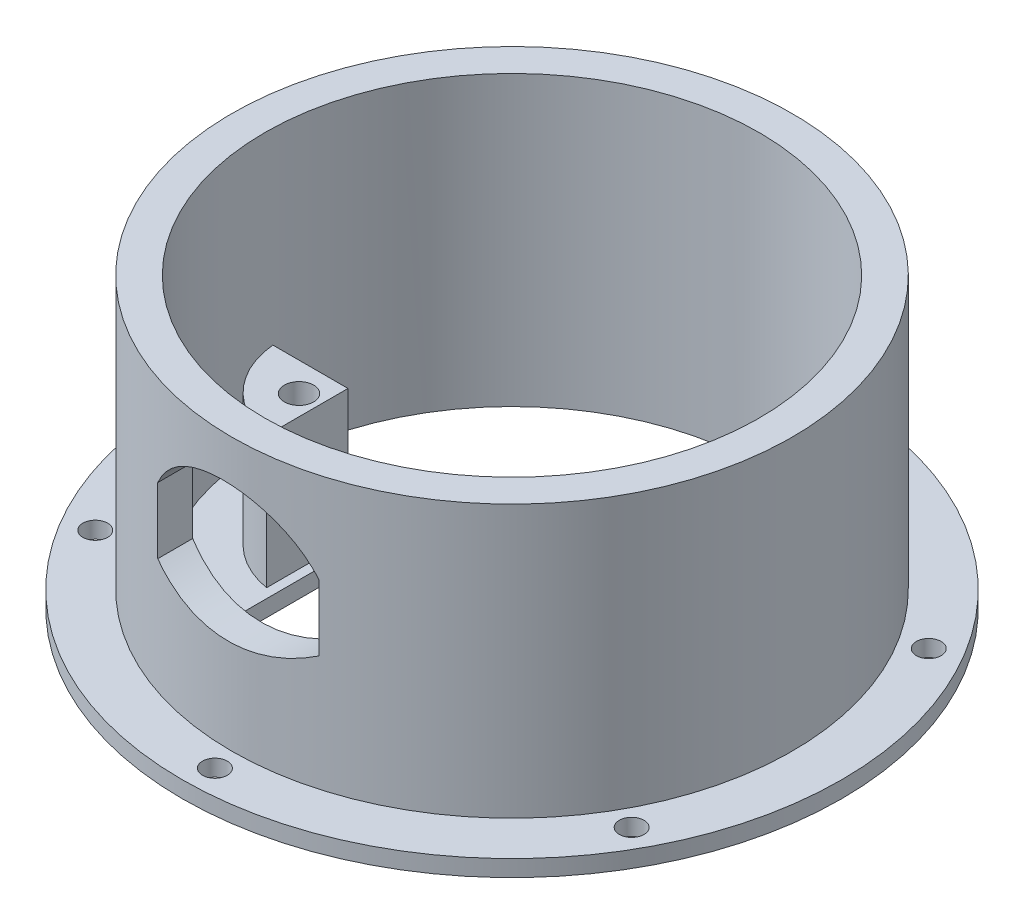
SolidWorks part; units mm, degrees
ref_plane "Front Plane" through (0, 0, 0) normal (0, 0, 1) x (1, 0, 0)
ref_plane "Top Plane" through (0, 0, 0) normal (0, 1, 0) x (1, 0, 0)
ref_plane "Right Plane" through (0, 0, 0) normal (1, 0, 0) x (0, 0, -1)
sketch "Sketch1" plane through (0, 0, 0) normal (0, 1, 0) x (1, 0, 0)
  circle A0 centre (0, 0) radius 40
  circle A1 centre (0, 0) radius 30
  dimension "D1" = 80
  dimension "D2" = 60
extrude "Boss-Extrude1" add sketch "Sketch1" along normal blind 2
sketch "Sketch2" plane through (0, 2, 0) normal (0, 1, 0) x (1, 0, 0)
  circle A0 centre (0, 0) radius 30 construction
  circle A1 centre (0, 0) radius 30
  circle A2 centre (0, 0) radius 34
  dimension "D1" = 4
extrude "Boss-Extrude2" add sketch "Sketch2" along normal blind 33
ref_plane "Plane1" through (0, 15, 0) normal (0, 1, 0) x (1, 0, 0)
sketch "Sketch9" plane through (0, 0, 0) normal (0, 1, 0) x (1, 0, 0)
  line L0 (-29.8657, -2.8351) -> (29.8657, -2.8351)
  line L1 (0, 30) -> (0, -48.3805) construction
  line L2 (-30, 0) -> (59.405, 0) construction
  circle A0 centre (0, 0) radius 30 construction
  arc A1 (29.8657, -2.8351) -> (0, -30) centre (0, 0) cw
  arc A2 (-29.8657, -2.8351) -> (0, -30) centre (0, 0) ccw
extrude "Boss-Extrude3" add sketch "Sketch9" along normal blind 2
sketch "Sketch11" plane through (0, 2, 0) normal (0, 1, 0) x (1, 0, 0)
  line L0 (-24.1735, -4.8351) -> (-15.0625, -4.8351)
  line L1 (-15.0625, -4.8351) -> (-15.0625, -14.7177)
  line L2 (0, 30) -> (0, 39.1404) construction
  line L3 (24.1735, -4.8351) -> (15.0625, -4.8351)
  line L4 (15.0625, -4.8351) -> (15.0625, -14.7177)
  line L5 (-29.8657, -2.8351) -> (29.8657, -2.8351) construction
  arc A0 (-24.1735, -4.8351) -> (-15.0625, -14.7177) centre (-13.1735, -3.8351) ccw
  arc A1 (24.1735, -4.8351) -> (15.0625, -14.7177) centre (13.1735, -3.8351) cw
  dimension "D1" = 2
ref_plane "Plane2" through (0, 0, 35) normal (0, 0, 1) x (1, 0, 0)
sketch "Sketch10" plane through (0, 0, 35) normal (0, 0, 1) x (1, 0, 0)
  line L1 (9.2889, 24.0041) -> (9.2889, 16.0041)
  line L2 (-10.7111, 24.0041) -> (-10.7111, 16.0041)
  arc A0 (9.2889, 16.0041) -> (-10.7111, 16.0041) centre (-0.7111, 33.4299) cw
  arc A1 (-10.7111, 24.0041) -> (9.2889, 24.0041) centre (-0.7111, 18.5894) cw
extrude "Cut-Extrude1" cut sketch "Sketch10" against normal blind 7
extrude "Boss-Extrude4" add sketch "Sketch11" along normal blind 16
sketch "Sketch12" plane through (0, 18, 0) normal (0, 1, 0) x (1, 0, 0)
  line L0 (0, 0) -> (0, 7.1822) construction
  line L1 (0, 30) -> (0, -48.3805) construction
  line L2 (-15.0625, -4.8351) -> (-24.1735, -4.8351) construction
  circle A0 centre (-17.5, -8.3351) radius 1.775
  circle A1 centre (17.5, -8.3351) radius 1.775
  dimension "D1" = 35
  dimension "D2" = 3.5
extrude "Cut-Extrude2" cut sketch "Sketch12" against normal blind 11
sketch "Sketch13" plane through (0, 2, 0) normal (0, 1, 0) x (1, 0, 0)
  line L0 (-13.9184, -20.8807) -> (-13.9184, 1.1193)
  line L1 (-13.9184, 1.1193) -> (14.0816, 1.1193)
  line L2 (14.0816, 1.1193) -> (14.0816, -20.8807)
  arc A0 (14.0816, -20.8807) -> (-13.9184, -20.8807) centre (0.0816, -8.9643) cw
  dimension "D1" = 28
extrude "Cut-Extrude3" cut sketch "Sketch13" against normal blind 10
sketch "Sketch14" plane through (0, 2, 0) normal (0, 1, 0) x (1, 0, 0)
  circle A0 centre (-0.7637, 36.8087) radius 1.5
  circle A1 centre (31.4954, 19.0657) radius 1.5
  circle A2 centre (32.2591, -17.7429) radius 1.5
  circle A3 centre (0.7637, -36.8087) radius 1.5
  circle A4 centre (-31.4954, -19.0657) radius 1.5
  circle A5 centre (-32.2591, 17.7429) radius 1.5
  point P14 (0, 0)
  dimension "D1" = 6
extrude "Cut-Extrude4" cut sketch "Sketch14" against normal up to surface (2 mm away) up to face at (0, 0, 40)
